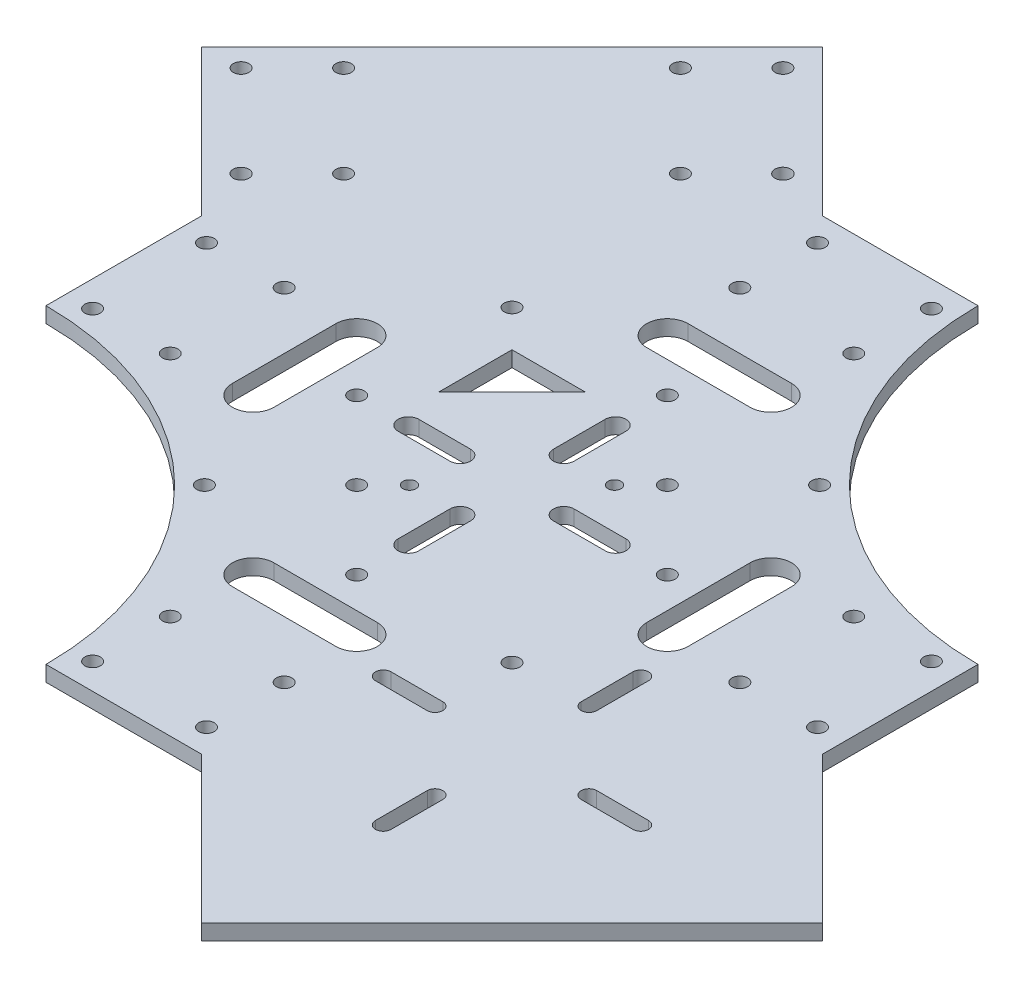
SolidWorks part; units mm, degrees
ref_plane "前视基准面" through (0, 0, 0) normal (0, 0, 1) x (1, 0, 0)
ref_plane "上视基准面" through (0, 0, 0) normal (0, 1, 0) x (1, 0, 0)
ref_plane "右视基准面" through (0, 0, 0) normal (1, 0, 0) x (0, 0, -1)
sketch "草图1" plane through (0, 0, 0) normal (0, 1, 0) x (1, 0, 0)
  line L0 (0, 0) -> (0, 75)
  line L1 (0, 0) -> (75, 0)
  line L2 (0, 0) -> (0, -75)
  line L3 (0, 0) -> (-75, 0)
  line L4 (0, 75) -> (15, 75)
  line L5 (0, 75) -> (-15, 75)
  line L6 (75, 0) -> (75, 15)
  line L7 (75, 0) -> (75, -15)
  line L8 (0, -75) -> (15, -75)
  line L9 (0, -75) -> (-15, -75)
  line L10 (-75, 0) -> (-75, -15)
  line L11 (-75, 0) -> (-75, 15)
  line L12 (75, 0) -> (70, 0)
  arc A0 (-75, 15) -> (-15, 75) centre (-75, 75) ccw
  arc A1 (15, 75) -> (75, 15) centre (75, 75) ccw
  arc A2 (75, -15) -> (15, -75) centre (75, -75) ccw
  arc A3 (-15, -75) -> (-75, -15) centre (-75, -75) ccw
  circle A4 centre (-11, 70) radius 1.25
  circle A5 centre (11, 70) radius 1.25
  circle A6 centre (70, -11) radius 1.25
  circle A7 centre (70, 11) radius 1.25
  circle A8 centre (-11, -70) radius 1.25
  circle A9 centre (11, -70) radius 1.25
  circle A10 centre (-70, 11) radius 1.25
  circle A11 centre (-70, -11) radius 1.25
  point P9 (0, 0)
  point P21 (0, 0)
  point P32 (0, 0)
  point P35 (0, 0)
  point P44 (0, 0)
  dimension "D1" = 4
extrude "凸台-拉伸1" add sketch "草图1" along normal blind 3 contours A2 L7 L1 L2 L8 A9 A6 | A3 L9 L2 L3 L10 A11 A8 | A0 L11 L3 L0 L5 A4 A10 | A1 L4 L0 L1 L6 A7 A5 region at (-25.2829, 0, -25.2829) region at (25.2829, 0, -25.2829) region at (25.2829, 0, 25.2829) region at (-25.2829, 0, 25.2829)
sketch "草图2" plane through (0, 0, 0) normal (0, -1, 0) x (1, 0, 0)
  line L0 (0, 0) -> (-32.5736, -32.5736)
  line L1 (0, 0) -> (32.5736, -32.5736)
  line L2 (-31.4663, 0.3536) -> (-0.3536, 31.4663)
  line L3 (31.4663, -0.3536) -> (-0.3536, 31.4663)
  line L4 (0.3536, -31.4663) -> (31.4663, -0.3536)
  line L5 (0.3536, -31.4663) -> (-31.4663, 0.3536)
  arc A0 (-15, -75) -> (-75, -15) centre (-75, -75) ccw construction
  circle A2 centre (0.3536, -31.4663) radius 1.5
  circle A3 centre (31.4663, -0.3536) radius 1.5
  circle A4 centre (-0.3536, 31.4663) radius 1.5
  circle A5 centre (-31.4663, 0.3536) radius 1.5
  point P12 (-15.5563, -15.5563)
  point P16 (-15.9099, 15.9099)
  point P17 (15.9099, -15.9099)
extrude "切除-拉伸1" cut sketch "草图2" against normal blind 3 contours A3 | A2 | A5 | A4
sketch "草图3" plane through (0, 3, 0) normal (0, 1, 0) x (1, 0, 0)
  line L0 (0.3536, 31.4663) -> (-31.4663, -0.3536)
  line L1 (-15.5563, 15.5563) -> (-22.6274, 22.6274)
  line L2 (-15.5563, 15.5563) -> (-12.0208, 19.0919)
  line L3 (-15.5563, 15.5563) -> (-19.0919, 12.0208)
  line L4 (-19.0919, 12.0208) -> (-22.6274, 22.6274)
  line L5 (-12.0208, 19.0919) -> (-22.6274, 22.6274)
extrude "切除-拉伸2" cut sketch "草图3" against normal blind 3 contours L0 L5 L1 | L4 L0 L1 region at (-16.7349, 3, -19.0919) region at (-19.0919, 3, -16.7349)
sketch "草图4" plane through (0, 3, 0) normal (0, 1, 0) x (1, 0, 0)
  line L0 (31.4663, 0.3536) -> (-0.3536, -31.4663)
  line L1 (0, 0) -> (21.2132, -21.2132)
  line L2 (28.2843, -14.1421) -> (14.1421, -28.2843)
  line L3 (14.1421, -28.2843) -> (28.2843, -14.1421) construction
  line L4 (8.4817, -22.6239) -> (22.6239, -8.4817)
  line L5 (19.8025, -33.9447) -> (33.9447, -19.8025)
  arc A0 (8.4817, -22.6239) -> (19.8025, -33.9447) centre (14.1421, -28.2843) ccw
  arc A1 (33.9447, -19.8025) -> (22.6239, -8.4817) centre (28.2843, -14.1421) ccw
  point P9 (21.2132, -21.2132)
extrude "切除-拉伸3" cut sketch "草图4" against normal blind 3 contours L5 A1 L0 A0 region at (21.2143, 3, 21.2143)
sketch "草图5" plane through (0, 3, 0) normal (0, 1, 0) x (1, 0, 0)
  line L0 (-12.0208, 19.0919) -> (-8.4853, 22.6274)
  line L1 (-8.4853, 22.6274) -> (-22.6274, 22.6274)
  line L2 (-19.0919, 12.0208) -> (-22.6274, 8.4853)
  line L3 (-22.6274, 8.4853) -> (-22.6274, 22.6274)
  line L4 (-12.0208, 19.0919) -> (-22.6274, 22.6274)
  line M28 (-19.0919, 12.0208) -> (-22.6274, 22.6274)
extrude "切除-拉伸4" cut sketch "草图5" against normal blind 10 contours L3 L2 M28 | L4 L0 L1 region at (-21.4489, 3, -14.3778)
sketch "草图6" plane through (0, 3, 0) normal (0, 1, 0) x (1, 0, 0)
  line L0 (0, 0) -> (-28.2843, -28.2843)
  line L1 (-28.2843, -28.2843) -> (-35.3553, -21.2132)
  line L2 (0, 0) -> (-22.6274, 22.6274)
  circle A0 centre (-35.3553, -21.2132) radius 1.5
  circle A1 centre (-21.2132, -35.3553) radius 1.5
  circle A2 centre (35.3553, 21.2132) radius 1.5
  circle A3 centre (21.2132, 35.3553) radius 1.5
extrude "切除-拉伸5" cut sketch "草图6" against normal blind 10 contours A1 | A0 | A2 | A3
sketch "草图7" plane through (0, 3, 0) normal (0, 1, 0) x (1, 0, 0)
  circle A0 centre (-29.6985, 29.6985) radius 1.5
  circle A1 centre (29.6985, 29.6985) radius 1.5
  circle A2 centre (29.6985, -29.6985) radius 1.5
  circle A3 centre (-29.6985, -29.6985) radius 1.5
  point P11 (0, 0)
  dimension "D1" = 4
extrude "切除-拉伸8" cut sketch "草图7" against normal blind 10
sketch "草图8" plane through (0, 3, 0) normal (0, 1, 0) x (1, 0, 0)
  circle A0 centre (-11, 55) radius 1.5
  circle A1 centre (11, 55) radius 1.5
  circle A2 centre (55, 11) radius 1.5
  circle A3 centre (55, -11) radius 1.5
  circle A4 centre (11, -55) radius 1.5
  circle A5 centre (-11, -55) radius 1.5
  circle A6 centre (-55, -11) radius 1.5
  circle A7 centre (-55, 11) radius 1.5
  point P21 (0, 0)
  dimension "D1" = 4
extrude "切除-拉伸9" cut sketch "草图8" against normal blind 10
sketch "草图9" plane through (0, 3, 0) normal (0, 1, 0) x (1, 0, 0)
  circle A0 centre (0, 0) radius 15
extrude "切除-拉伸10" cut sketch "草图9" against normal blind 10
sketch "草图11" plane through (0, 3, 0) normal (0, 1, 0) x (1, 0, 0)
  circle A0 centre (-35.3553, -21.2132) radius 1.5
  circle A2 centre (35.3553, 21.2132) radius 1.5
  circle A3 centre (21.2132, 35.3553) radius 1.5
  circle A4 centre (0.3536, 31.4663) radius 1.5
  circle A5 centre (31.4663, 0.3536) radius 1.5
  circle A6 centre (-0.3536, -31.4663) radius 1.5
  circle A7 centre (-31.4663, -0.3536) radius 1.5
  circle A8 centre (-21.2132, -35.3553) radius 1.5
extrude "凸台-拉伸3" add sketch "草图11" against normal blind 3
sketch "草图12" plane through (0, 3, 0) normal (0, 1, 0) x (1, 0, 0)
  line L0 (0, 0) -> (-40, 0)
  line L1 (-40, 0) -> (-40, 10)
  line L2 (-40, 0) -> (-40, -10)
  line L3 (-40, -10) -> (-40, 10) construction
  line L4 (-44, -10) -> (-44, 10)
  line L5 (-36, -10) -> (-36, 10)
  line L6 (-10, 40) -> (10, 40) construction
  line L7 (-10, 44) -> (10, 44)
  line L8 (-10, 36) -> (10, 36)
  line L9 (40, 10) -> (40, -10) construction
  line L10 (44, 10) -> (44, -10)
  line L11 (36, 10) -> (36, -10)
  line L12 (10, -40) -> (-10, -40) construction
  line L13 (10, -44) -> (-10, -44)
  line L14 (10, -36) -> (-10, -36)
  arc A0 (-44, -10) -> (-36, -10) centre (-40, -10) ccw
  arc A1 (-36, 10) -> (-44, 10) centre (-40, 10) ccw
  arc A2 (-10, 44) -> (-10, 36) centre (-10, 40) ccw
  arc A3 (10, 36) -> (10, 44) centre (10, 40) ccw
  arc A4 (44, 10) -> (36, 10) centre (40, 10) ccw
  arc A5 (36, -10) -> (44, -10) centre (40, -10) ccw
  arc A6 (10, -44) -> (10, -36) centre (10, -40) ccw
  arc A7 (-10, -36) -> (-10, -44) centre (-10, -40) ccw
  point P3 (-40, 0)
  point P13 (0, 40)
  point P20 (40, 0)
  point P27 (0, -40)
  point P34 (0, 0)
  dimension "D1" = 4
extrude "切除-拉伸12" cut sketch "草图12" against normal blind 3 contours L5 A1 L4 A0 | L8 A3 L7 A2 | L11 A5 L10 A4 | L14 A7 L13 A6 region at (-43.7088, 3, 0) region at (0, 3, -40) region at (40, 3, 0) region at (0, 3, 40)
sketch "草图14" plane through (0, 3, 0) normal (0, 1, 0) x (1, 0, 0)
  line L0 (22.8277, -8.285) -> (8.285, -22.8277) construction
  line L1 (19.8025, -33.9447) -> (33.9447, -19.8025) construction
  line L2 (8.285, -22.8277) -> (22.8277, -8.285)
  line L3 (22.8277, -8.285) -> (19.8025, -33.9447)
  line L4 (19.8025, -33.9447) -> (33.9447, -19.8025)
  arc A0 (8.285, -22.8277) -> (19.8025, -33.9447) centre (14.1421, -28.2843) ccw
  arc A1 (8.285, -22.8277) -> (19.8025, -33.9447) centre (14.1421, -28.2843) ccw construction
  arc A2 (33.9447, -19.8025) -> (22.8277, -8.285) centre (28.2843, -14.1421) ccw construction
  arc A3 (22.8277, -8.285) -> (32.1857, -7.1522) centre (28.2843, -14.1421) ccw
  circle A4 centre (28.2843, -14.1421) radius 8.005
extrude "凸台-拉伸4" add sketch "草图14" against normal blind 3 contours A3 A4 L3 | L2 A3 L3 | A3 L2 A0 L3 | A3 L3 L4 region at (14.6624, 3, 25.7239) region at (21.4582, 3, 13.3381) region at (24.21, 3, 25.4431) region at (28.7736, 3, 14.1998)
sketch "草图15" plane through (0, 3, 0) normal (0, 1, 0) x (1, 0, 0)
  circle A0 centre (0, 0) radius 15
extrude "凸台-拉伸5" add sketch "草图15" against normal blind 3
sketch "草图17" plane through (0, 3, 0) normal (0, 1, 0) x (1, 0, 0)
  line L0 (0, 0) -> (0, -20)
  line L1 (0, -20) -> (0, -10) construction
  line L2 (-2, -20) -> (-2, -10)
  line L3 (2, -20) -> (2, -10)
  line L4 (-20, 0) -> (-10, 0) construction
  line L5 (-20, 2) -> (-10, 2)
  line L6 (-20, -2) -> (-10, -2)
  line L7 (0, 20) -> (0, 10) construction
  line L8 (2, 20) -> (2, 10)
  line L9 (-2, 20) -> (-2, 10)
  line L10 (20, 0) -> (10, 0) construction
  line L11 (20, -2) -> (10, -2)
  line L12 (20, 2) -> (10, 2)
  arc A0 (-2, -20) -> (2, -20) centre (0, -20) ccw
  arc A1 (2, -10) -> (-2, -10) centre (0, -10) ccw
  arc A2 (-20, 2) -> (-20, -2) centre (-20, 0) ccw
  arc A3 (-10, -2) -> (-10, 2) centre (-10, 0) ccw
  arc A4 (2, 20) -> (-2, 20) centre (0, 20) ccw
  arc A5 (-2, 10) -> (2, 10) centre (0, 10) ccw
  arc A6 (20, -2) -> (20, 2) centre (20, 0) ccw
  arc A7 (10, 2) -> (10, -2) centre (10, 0) ccw
  point P3 (0, -15)
  point P13 (-15, 0)
  point P20 (0, 15)
  point P27 (15, 0)
  point P33 (0, 0)
  dimension "D1" = 4
extrude "切除-拉伸13" cut sketch "草图17" against normal blind 3 contours L8 A5 L9 A4 | L12 A7 L11 A6 | L3 A1 L2 A0 | L5 A3 L6 A2
sketch "草图18" plane through (0, 3, 0) normal (0, 1, 0) x (1, 0, 0)
  line L0 (0, 0) -> (-32.5736, 32.5736)
  line L1 (-32.5736, 32.5736) -> (-46.7157, 46.7157)
  line L2 (-50.2513, 50.2513) -> (-61.9773, 38.5252)
  line L3 (-46.7157, 46.7157) -> (-50.2513, 50.2513)
  line L4 (-61.9773, 38.5252) -> (-38.5252, 61.9773)
  line L5 (-38.5252, 61.9773) -> (-22.5002, 45.9523)
  line L6 (-61.9773, 38.5252) -> (-45.9523, 22.5002)
  arc A0 (-75, 15) -> (-15, 75) centre (-75, 75) ccw construction
  circle A1 centre (-67.9289, 67.9289) radius 30
  circle A2 centre (-75, 75) radius 60
extrude "凸台-拉伸7" add sketch "草图18" against normal blind 3 contours L4 A1 L2 | L2 A1 L3 | L3 A1 L4 | L6 A2 L1 A1 | L1 A2 L5 A1 region at (-46.4984, 3, -34.5306) region at (-34.5306, 3, -46.4984) region at (-53.277, 3, -44.3758) region at (-44.3758, 3, -53.277) region at (-68.7208, 3, -68.7208)
sketch "草图19" plane through (0, 3, 0) normal (0, 1, 0) x (1, 0, 0)
  line L0 (-61.9773, 38.5252) -> (-38.5252, 61.9773)
  line L1 (-50.2513, 50.2513) -> (-36.1091, 36.1091)
  line L2 (-36.1091, 36.1091) -> (-43.1802, 29.0381)
  line L3 (-36.1091, 36.1091) -> (-29.0381, 43.1802)
  line L4 (-29.0381, 43.1802) -> (-37.1408, 51.2829)
  line L5 (-37.1408, 51.2829) -> (-51.2829, 37.1408)
  line L6 (-51.2829, 37.1408) -> (-43.1802, 29.0381)
  circle A1 centre (-67.9289, 67.9289) radius 35
  circle A2 centre (-67.9289, 67.9289) radius 45
extrude "切除-拉伸14" cut sketch "草图19" against normal blind 3 contours L1 A2 L4 A1 | L6 A2 L1 A1 region at (-36.3949, 3, -43.5045) region at (-43.5045, 3, -36.3949)
sketch "草图21" plane through (0, 3, 0) normal (0, 1, 0) x (1, 0, 0)
  line L0 (-61.9773, 38.5252) -> (-38.5252, 61.9773)
  line L1 (-67.9289, 67.9289) -> (-53.7868, 53.7868)
  line L2 (-82.0711, 82.0711) -> (-75, 75)
  line L3 (-67.9289, 67.9289) -> (-82.0711, 82.0711)
  line L4 (-53.7868, 53.7868) -> (-60.8579, 60.8579)
  line L5 (-82.0711, 82.0711) -> (-75, 75) construction
  line L6 (-81.1872, 82.955) -> (-74.1161, 75.8839)
  line L7 (-82.955, 81.1872) -> (-75.8839, 74.1161)
  line L8 (-60.8579, 60.8579) -> (-53.7868, 53.7868) construction
  line L9 (-59.974, 61.7417) -> (-52.9029, 54.6707)
  line L10 (-61.7417, 59.974) -> (-54.6707, 52.9029)
  arc A0 (-81.1872, 82.955) -> (-82.955, 81.1872) centre (-82.0711, 82.0711) ccw
  arc A1 (-75.8839, 74.1161) -> (-74.1161, 75.8839) centre (-75, 75) ccw
  arc A2 (-59.974, 61.7417) -> (-61.7417, 59.974) centre (-60.8579, 60.8579) ccw
  arc A3 (-54.6707, 52.9029) -> (-52.9029, 54.6707) centre (-53.7868, 53.7868) ccw
  point P2 (-78.5355, 78.5355)
  point P15 (-57.3223, 57.3223)
extrude "切除-拉伸15" cut sketch "草图21" against normal blind 3 contours A1 L6 A0 L7 | A3 L9 A2 L10 region at (-75, 3, -73.8854)
pattern_circular "阵列(圆周)1" count 8 over 360 about axis through (-67.9289, 3, -67.9289) along (0, 1, 0) of "切除-拉伸15"
sketch "草图22" plane through (0, 3, 0) normal (0, 1, 0) x (1, 0, 0)
  line L0 (0, 0) -> (9.8995, 9.8995)
  line L1 (0, 0) -> (-9.8995, -9.8995)
  circle A0 centre (9.8995, 9.8995) radius 1.25
  circle A1 centre (-9.8995, -9.8995) radius 1.25
extrude "切除-拉伸17" cut sketch "草图22" against normal blind 3 contours A0 | A1
sketch "草图23" plane through (0, 3, 0) normal (0, 1, 0) x (1, 0, 0)
  circle A0 centre (0, 30) radius 1.5
  circle A1 centre (30, 0) radius 1.5
  circle A2 centre (0, -30) radius 1.5
  circle A3 centre (-30, 0) radius 1.5
  point P13 (0, 0)
  dimension "D1" = 4
extrude "切除-拉伸18" cut sketch "草图23" against normal blind 10
sketch "草图24" plane through (0, 3, 0) normal (0, 1, 0) x (1, 0, 0)
  circle A0 centre (-15, -15) radius 1.5
  circle A1 centre (15, 15) radius 1.5
extrude "切除-拉伸19" cut sketch "草图24" against normal blind 10
sketch "草图25" plane through (0, 3, 0) normal (0, 1, 0) x (1, 0, 0)
  circle A0 centre (-75, 75) radius 60
extrude "切除-拉伸20" cut sketch "草图25" against normal blind 10
sketch "草图26" plane through (0, 3, 0) normal (0, 1, 0) x (1, 0, 0)
  line L0 (-15, 75) -> (-75, 15)
  circle A0 centre (-75, 75) radius 60
extrude "凸台-拉伸8" add sketch "草图26" against normal blind 3 contours L0 A0 region at (-39.9612, 3, -39.9612)
sketch "草图27" plane through (0, 0, 0) normal (0, -1, 0) x (1, 0, 0)
  line L0 (-45, -45) -> (-23.5998, -66.4002)
  line L1 (-15, -75) -> (-75, -15) construction
  line L2 (-23.5998, -66.4002) -> (-66.0262, -23.9738)
  line L3 (-15, -75) -> (-22.0711, -82.0711)
  line L4 (-22.0711, -82.0711) -> (-75, -15)
  line L5 (-75, -15) -> (-82.0711, -22.0711)
  line L6 (-82.0711, -22.0711) -> (-22.0711, -82.0711)
  line L7 (75, 15) -> (15, 75)
  line L8 (15, 75) -> (22.0711, 82.0711)
  line L9 (75, 15) -> (82.0711, 22.0711)
  line L10 (82.0711, 22.0711) -> (22.0711, 82.0711)
  line L11 (-15, -75) -> (-75, -15)
  line L12 (-22.0711, -82.0711) -> (-29.1421, -89.1421)
  line L13 (-29.1421, -89.1421) -> (-82.0711, -22.0711)
  line L14 (-82.0711, -22.0711) -> (-89.1421, -29.1421)
  line L15 (-89.1421, -29.1421) -> (-29.1421, -89.1421)
  circle A0 centre (75, 75) radius 60
extrude "凸台-拉伸10" add sketch "草图27" against normal blind 3 contours L14 L15 L13 | L13 L12 L6 | L5 L6 L4 | L3 L11 L0 L2 L4 region at (-37.357, 0, -57.357) region at (-59.714, 0, -39.714) region at (-44.4281, 0, -64.4281) region at (-66.7851, 0, -46.7851)
sketch "草图28" plane through (0, 0, 0) normal (0, -1, 0) x (1, 0, 0)
  line L0 (-59.1421, -59.1421) -> (-52.0711, -52.0711)
  line L1 (-89.1421, -29.1421) -> (-29.1421, -89.1421) construction
  line L2 (-52.0711, -52.0711) -> (-25.9081, -78.234)
  line L3 (-52.0711, -52.0711) -> (-78.234, -25.9081)
  line L4 (11, -70) -> (8.198, -68.4493)
  circle A1 centre (11, -70) radius 1.5
  circle A2 centre (-11, -70) radius 1.5
  circle A3 centre (-70, -11) radius 1.5
  circle A4 centre (-70, 11) radius 1.5
  circle A5 centre (-11, 70) radius 1.5
  circle A6 centre (11, 70) radius 1.5
  circle A7 centre (70, 11) radius 1.5
  circle A8 centre (70, -11) radius 1.5
  circle A9 centre (-25.9081, -78.234) radius 1.54
  circle A10 centre (-78.234, -25.9081) radius 1.52
extrude "切除-拉伸21" cut sketch "草图28" against normal blind 3 contours A9 | A10 | A3 | A4 | A2 | A1 | A8 | A7 | A5 | A6 region at (-25.3355, 0, -76.8515) region at (-79.5986, 0, -25.3429)
sketch "草图29" plane through (0, 0, 0) normal (0, -1, 0) x (1, 0, 0)
  line L0 (-59.1421, -59.1421) -> (-22.6274, -22.6274)
  line L1 (-78.234, -25.9081) -> (-68.3345, -35.8076)
  line L2 (-89.1421, -29.1421) -> (-29.1421, -89.1421) construction
  circle A0 centre (-68.3345, -35.8076) radius 1.5
  circle A1 centre (-35.8076, -68.3345) radius 1.5
extrude "切除-拉伸22" cut sketch "草图29" against normal blind 3 contours A1 | A0
sketch "草图30" plane through (0, 0, 0) normal (0, -1, 0) x (1, 0, 0)
  line L0 (-29.1421, -89.1421) -> (-89.1421, -29.1421)
  line L1 (-29.1421, -89.1421) -> (-43.2843, -103.2843)
  line L2 (-89.1421, -29.1421) -> (-103.2843, -43.2843)
  line L3 (-43.2843, -103.2843) -> (-103.2843, -43.2843)
extrude "凸台-拉伸11" add sketch "草图30" against normal blind 3
sketch "草图31" plane through (0, 0, 0) normal (0, -1, 0) x (1, 0, 0)
  line L1 (-25.9081, -78.234) -> (-78.234, -25.9081)
  circle A0 centre (-43.5858, -95.9117) radius 1.5
  circle A1 centre (-53.4853, -86.0122) radius 1.5
  circle A2 centre (-86.0122, -53.4853) radius 1.5
  circle A3 centre (-95.9117, -43.5858) radius 1.5
extrude "切除-拉伸23" cut sketch "草图31" against normal blind 3 contours A0 | A1 | A2 | A3
sketch "草图32" plane through (0, 0, 0) normal (0, -1, 0) x (1, 0, 0)
  line L0 (75, 15) -> (15, 75)
  line L1 (75, 15) -> (15, 75)
  line L2 (75, 15) -> (89.1421, 29.1421)
  line L3 (15, 75) -> (29.1421, 89.1421)
  line L4 (89.1421, 29.1421) -> (29.1421, 89.1421)
  circle A0 centre (75, 75) radius 60
extrude "凸台-拉伸12" add sketch "草图32" against normal blind 3 contours L0 A0 | L2 L4 L3 L0 region at (39.9612, 0, 39.9612) region at (52.0711, 0, 52.0711)
sketch "草图33" plane through (0, 0, 0) normal (0, -1, 0) x (-1, 0, 0)
  line L0 (-29.6985, -29.6985) -> (-59.1421, -59.1421)
  line L1 (-89.1421, -29.1421) -> (-29.1421, -89.1421) construction
  line L2 (-44.4203, -44.4203) -> (-14.6894, -44.4203)
  line L3 (-14.6894, -44.4203) -> (-44.4203, -16.8394)
  line L4 (-44.4203, -16.8394) -> (-44.4203, -44.4203)
  line L5 (-29.5549, -44.4203) -> (-19.5549, -44.4203) construction
  line L6 (-29.5549, -42.92) -> (-19.5549, -42.92)
  line L7 (-29.5549, -45.9207) -> (-19.5549, -45.9207)
  line L8 (-44.4203, -59.2858) -> (-44.4203, -69.2858) construction
  line L9 (-42.92, -59.2858) -> (-42.92, -69.2858)
  line L10 (-45.9207, -59.2858) -> (-45.9207, -69.2858)
  line L11 (-59.2858, -44.4203) -> (-69.2858, -44.4203) construction
  line L12 (-59.2858, -45.9207) -> (-69.2858, -45.9207)
  line L13 (-59.2858, -42.92) -> (-69.2858, -42.92)
  line L14 (-44.4203, -29.5549) -> (-44.4203, -19.5549) construction
  line L15 (-45.9207, -29.5549) -> (-45.9207, -19.5549)
  line L16 (-42.92, -29.5549) -> (-42.92, -19.5549)
  arc A0 (-29.5549, -42.92) -> (-29.5549, -45.9207) centre (-29.5549, -44.4203) ccw
  arc A1 (-19.5549, -45.9207) -> (-19.5549, -42.92) centre (-19.5549, -44.4203) ccw
  arc A2 (-42.92, -59.2858) -> (-45.9207, -59.2858) centre (-44.4203, -59.2858) ccw
  arc A3 (-45.9207, -69.2858) -> (-42.92, -69.2858) centre (-44.4203, -69.2858) ccw
  arc A4 (-59.2858, -45.9207) -> (-59.2858, -42.92) centre (-59.2858, -44.4203) ccw
  arc A5 (-69.2858, -42.92) -> (-69.2858, -45.9207) centre (-69.2858, -44.4203) ccw
  arc A6 (-45.9207, -29.5549) -> (-42.92, -29.5549) centre (-44.4203, -29.5549) ccw
  arc A7 (-42.92, -19.5549) -> (-45.9207, -19.5549) centre (-44.4203, -19.5549) ccw
  point P10 (-24.5549, -44.4203)
  point P20 (-44.4203, -64.2858)
  point P27 (-64.2858, -44.4203)
  point P34 (-44.4203, -24.5549)
  point P39 (-44.4203, -44.4203)
  dimension "D1" = 4
extrude "切除-拉伸24" cut sketch "草图33" against normal blind 3 contours L10 A3 L9 A2 | L7 A1 L6 A0 | L12 A5 L13 A4 | L15 A7 L16 A6
sketch "草图34" plane through (0, 0, 0) normal (0, -1, 0) x (1, 0, 0)
  line L0 (29.1421, 89.1421) -> (89.1421, 29.1421)
  line L1 (29.1421, 89.1421) -> (43.2843, 103.2843)
  line L2 (89.1421, 29.1421) -> (103.2843, 43.2843)
  line L3 (43.2843, 103.2843) -> (103.2843, 43.2843)
  line L4 (75, 15) -> (89.1421, 29.1421) construction
  line L5 (89.1421, 29.1421) -> (29.1421, 89.1421) construction
extrude "凸台-拉伸13" add sketch "草图34" against normal blind 3
